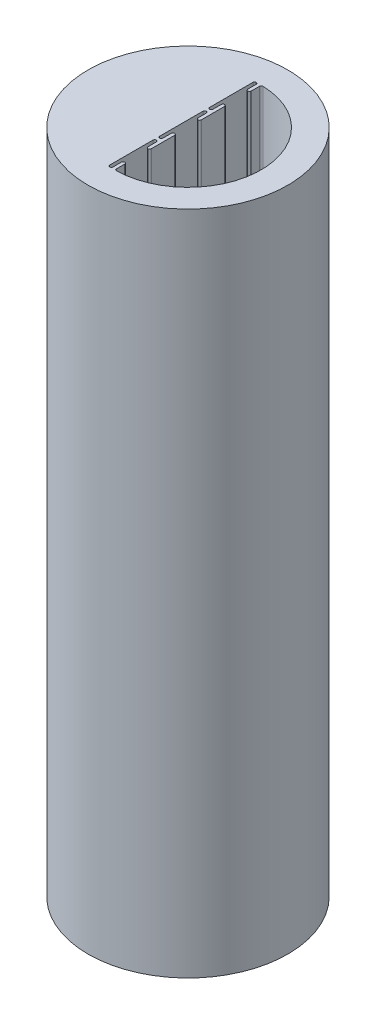
SolidWorks part; units mm, degrees
ref_plane "Front Plane" through (0, 0, 0) normal (0, 0, 1) x (1, 0, 0)
ref_plane "Top Plane" through (0, 0, 0) normal (0, 1, 0) x (1, 0, 0)
ref_plane "Right Plane" through (0, 0, 0) normal (1, 0, 0) x (0, 0, -1)
sketch "Sketch1" plane through (0, 0, 0) normal (0, 1, 0) x (1, 0, 0)
  line L0 (-26.4187, -4.176) -> (-26.4187, -18.176)
  line L1 (-26.4187, -18.176) -> (-25.4187, -18.176)
  line L2 (-25.4187, -18.176) -> (-25.4187, -14.676)
  line L3 (-25.4187, -14.676) -> (-24.4187, -14.676)
  line L4 (-24.4187, -14.676) -> (-24.4187, -18.176)
  line L13 (-24.4187, -4.176) -> (-24.4187, -7.676)
  line L14 (-24.4187, -7.676) -> (-25.4187, -7.676)
  line L15 (-25.4187, -7.676) -> (-25.4187, -4.176)
  line L16 (-25.4187, -4.176) -> (-26.4187, -4.176)
  line L17 (-26.4187, 10.824) -> (-26.4187, -3.176)
  line L18 (-26.4187, -3.176) -> (-25.4187, -3.176)
  line L19 (-25.4187, -3.176) -> (-25.4187, 0.324)
  line L20 (-25.4187, 0.324) -> (-24.4187, 0.324)
  line L21 (-24.4187, 0.324) -> (-24.4187, -3.176)
  line L22 (-24.4187, 10.824) -> (-24.4187, 7.324)
  line L23 (-24.4187, 7.324) -> (-25.4187, 7.324)
  line L24 (-25.4187, 7.324) -> (-25.4187, 10.824)
  line L25 (-25.4187, 10.824) -> (-26.4187, 10.824)
  line L35 (-26.4187, -4.176) -> (-26.4187, 10.824) construction
  line L40 (-26.4187, 25.824) -> (-26.4187, 11.824)
  line L41 (-26.4187, 11.824) -> (-25.4187, 11.824)
  line L42 (-25.4187, 11.824) -> (-25.4187, 15.324)
  line L43 (-25.4187, 15.324) -> (-24.4187, 15.324)
  line L44 (-24.4187, 15.324) -> (-24.4187, 11.824)
  line L45 (-24.4187, 25.824) -> (-24.4187, 22.324)
  line L46 (-24.4187, 22.324) -> (-25.4187, 22.324)
  line L47 (-25.4187, 22.324) -> (-25.4187, 25.824)
  line L48 (-25.4187, 25.824) -> (-26.4187, 25.824)
  line L49 (-24.4187, 11.824) -> (-24.4187, 10.824)
  line L50 (-24.4187, -3.176) -> (-24.4187, -4.176)
  arc A0 (-24.4187, -18.176) -> (-24.4187, 25.824) centre (-24.4187, 3.824) ccw
  circle A1 centre (-24.4187, 3.824) radius 30
  dimension "D7" = 60
  dimension "D1" = 7
  dimension "D2" = 3
  dimension "D3" = 1
  dimension "D4" = 14
  dimension "D5" = 1
  dimension "D6" = 15
extrude "Boss-Extrude2" add sketch "Sketch1" along normal blind 200 contours L35 L16 L15 L14 L13 L50 L21 L20 L19 L18 | A1 L0 L35 L17 L25 L24 L23 L22 L49 L44 L43 L42 L41 L40 L48 L47 L46 L45 A0 L4 L3 L2 L1 region at (-25.0298, 0, 3.676) region at (-27.937, 0, -3.8578)
fillet "Fillet1" radius 0.5 26 edges at (-24.4187, 100, -25.824) (-25.4187, 100, 3.176) (-25.4187, 100, -0.324) (-25.4187, 100, -15.324) (-25.4187, 100, -11.824) (-25.4187, 100, -25.824) (-25.4187, 100, -22.324) (-25.4187, 100, -7.324) (-25.4187, 100, -10.824) (-25.4187, 100, 4.176) (-24.4187, 100, -0.324) (-24.4187, 100, -15.324) (-26.4187, 100, -11.824) (-26.4187, 100, 3.176) (-26.4187, 100, -25.824) (-24.4187, 100, -22.324) (-24.4187, 100, -7.324) (-26.4187, 100, -10.824) (-26.4187, 100, 4.176) (-24.4187, 100, 7.676) (-25.4187, 100, 7.676) (-25.4187, 100, 14.676) (-24.4187, 100, 14.676) (-24.4187, 100, 18.176) (-26.4187, 100, 18.176) (-25.4187, 100, 18.176)
